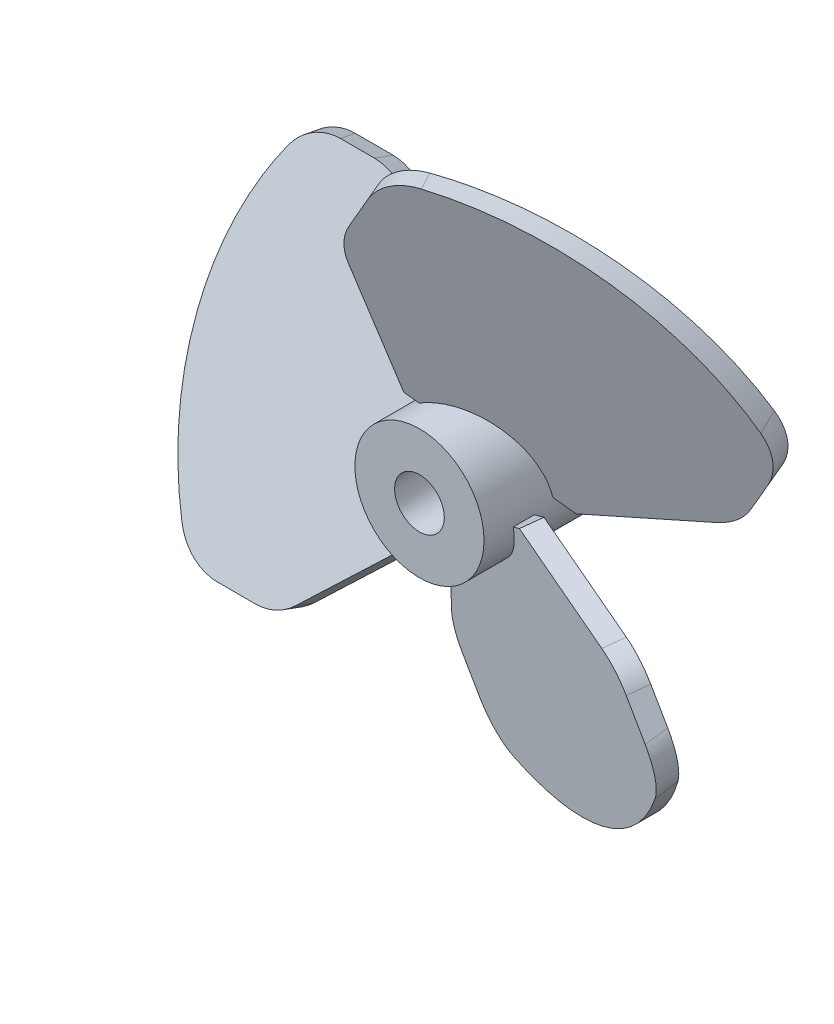
SolidWorks part; units mm, degrees
ref_plane "Front Plane" through (0, 0, 0) normal (0, 0, 1) x (1, 0, 0)
ref_plane "Top Plane" through (0, 0, 0) normal (0, 1, 0) x (1, 0, 0)
ref_plane "Right Plane" through (0, 0, 0) normal (1, 0, 0) x (0, 0, -1)
sketch "Sketch1" plane through (0, 0, 0) normal (0, 0, 1) x (1, 0, 0)
  circle A0 centre (0, 0) radius 2.5
  circle A1 centre (0, 0) radius 6.5
extrude "Boss-Extrude1" add sketch "Sketch1" against normal blind 12
sketch "Sketch2" plane through (-3.5, 0, 0) normal (-1, 0, 0) x (0, 0, 1)
  line L0 (-6, -0.0087) -> (-6, 6.5) construction
  line L1 (0, 6.5) -> (-12, 6.5) construction
  line L2 (-12.925, 16.0939) -> (-0.9543, -16.7953)
  line L3 (-0.9543, -16.7953) -> (0.925, -16.1113)
  line L4 (0.925, -16.1113) -> (-11.0457, 16.7779)
  line L5 (-11.0457, 16.7779) -> (-12.925, 16.0939)
  dimension "D1" = 20
  dimension "D2" = 35
  dimension "D3" = 17.5
  dimension "D4" = 1
  dimension "D5" = 2
extrude "Boss-Extrude2" add sketch "Sketch2" along normal blind 35
pattern_circular "CirPattern1" count 3 every 120 about axis through (0, 0, 0) along (0, 0, 1) of "Boss-Extrude2"
sketch "Sketch3" plane through (0, 0, 0) normal (0, 0, 1) x (1, 0, 0)
  circle A0 centre (0, 0) radius 27.5
  circle A1 centre (0, 0) radius 41.997
extrude "Cut-Extrude1" cut sketch "Sketch3" against normal through all both and the other way through all
chamfer "Chamfer1" distance 10 angle 45 6 edges at (-3.5, 16.4359, -11.9854) (-3.5, -16.4533, -0.0146) (-12.4839, -11.249, -11.9854) (15.999, 5.1956, -0.0146) (15.9839, -5.1869, -11.9854) (-12.499, 11.2577, -0.0146)
fillet "Fillet1" radius 5 12 edges at (-7.499, 19.918, -0.0146) (-3.234, 27.3092, -0.0201) (25.2589, 10.8738, -11.9799) (20.9839, 3.4734, -11.9854) (20.999, -3.4647, -0.0146) (25.2674, -10.8539, -0.0201) (-3.2124, -27.3117, -11.9799) (-7.4839, -19.9093, -11.9854) (-13.5, -16.4533, -0.0146) (-22.0335, -16.4553, -0.0201) (-13.5, 16.4359, -11.9854) (-22.0464, 16.4379, -11.9799)
